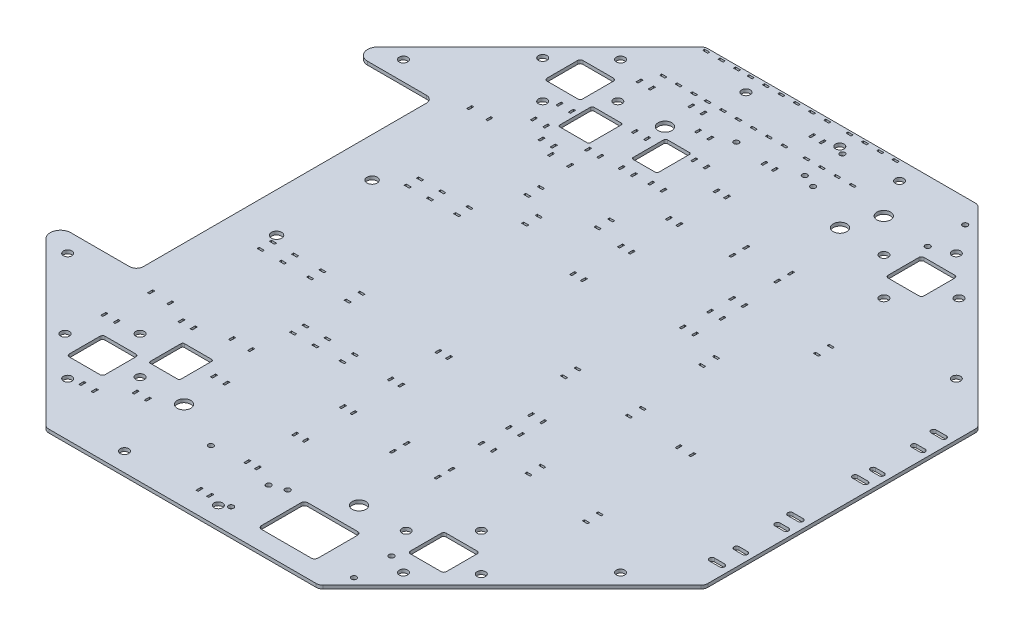
SolidWorks part; units mm, degrees
ref_plane "前视基准面" through (0, 0, 0) normal (0, 0, 1) x (1, 0, 0)
ref_plane "上视基准面" through (0, 0, 0) normal (0, 1, 0) x (1, 0, 0)
ref_plane "右视基准面" through (0, 0, 0) normal (1, 0, 0) x (0, 0, -1)
other "Configuration Table"
ref_plane "基准面1" through (0, 0, 0) normal (0, -1, 0) x (1, 0, 0)
sketch "草图1" plane through (0, 0, 0) normal (0, -1, 0) x (1, 0, 0)
  line L0 (-175.8944, -97.2426) -> (-81.1716, -191.9655)
  line L1 (-78.3431, -193.1371) -> (78.3431, -193.1371)
  line L2 (81.1716, -191.9655) -> (191.9655, -81.1716)
  line L3 (193.1371, -78.3431) -> (193.1371, 78.3431)
  line L4 (191.9655, 81.1716) -> (81.1716, 191.9655)
  line L5 (78.3431, 193.1371) -> (-78.3431, 193.1371)
  line L6 (-81.1716, 191.9655) -> (-175.8944, 97.2426)
  line L7 (-171.6518, 87) -> (-137.1371, 87)
  line L8 (-133.1371, 83) -> (-133.1371, -83)
  line L9 (-137.1371, -87) -> (-171.6518, -87)
  line L10 (182.1371, -63.5) -> (188.1371, -63.5)
  line L11 (188.1371, -66.5) -> (182.1371, -66.5)
  line L12 (182.1371, -17.5) -> (188.1371, -17.5)
  line L13 (188.1371, -20.5) -> (182.1371, -20.5)
  line L14 (182.1371, 66.5) -> (188.1371, 66.5)
  line L15 (188.1371, 63.5) -> (182.1371, 63.5)
  line L16 (182.1371, 20.5) -> (188.1371, 20.5)
  line L17 (188.1371, 17.5) -> (182.1371, 17.5)
  line L18 (183.6371, 53.5) -> (188.6371, 53.5)
  line L19 (188.6371, 50.5) -> (183.6371, 50.5)
  line L20 (188.6371, 26.5) -> (183.6371, 26.5)
  line L21 (183.6371, 29.5) -> (188.6371, 29.5)
  line L22 (188.6371, -53.5) -> (183.6371, -53.5)
  line L23 (183.6371, -50.5) -> (188.6371, -50.5)
  line L24 (183.6371, -26.5) -> (188.6371, -26.5)
  line L25 (188.6371, -29.5) -> (183.6371, -29.5)
  line L26 (-45, -134) -> (-45, -116)
  line L27 (-44, -115) -> (-31, -115)
  line L28 (-30, -116) -> (-30, -134)
  line L29 (-31, -135) -> (-44, -135)
  line L30 (-95, -43.2) -> (-98, -43.2)
  line L31 (-98, -43.2) -> (-98, -42)
  line L32 (-98, -42) -> (-95, -42)
  line L33 (-95, -42) -> (-95, -43.2)
  line L34 (-95, -36) -> (-98, -36)
  line L35 (-98, -36) -> (-98, -34.8)
  line L36 (-98, -34.8) -> (-95, -34.8)
  line L37 (-95, -34.8) -> (-95, -36)
  line L38 (-82, -43.2) -> (-85, -43.2)
  line L39 (-85, -43.2) -> (-85, -42)
  line L40 (-85, -42) -> (-82, -42)
  line L41 (-82, -42) -> (-82, -43.2)
  line L42 (-82, -36) -> (-85, -36)
  line L43 (-85, -36) -> (-85, -34.8)
  line L44 (-85, -34.8) -> (-82, -34.8)
  line L45 (-82, -34.8) -> (-82, -36)
  line L46 (-66, -43.2) -> (-69, -43.2)
  line L47 (-69, -43.2) -> (-69, -42)
  line L48 (-69, -42) -> (-66, -42)
  line L49 (-66, -42) -> (-66, -43.2)
  line L50 (-66, -36) -> (-69, -36)
  line L51 (-69, -36) -> (-69, -34.8)
  line L52 (-69, -34.8) -> (-66, -34.8)
  line L53 (-66, -34.8) -> (-66, -36)
  line L54 (-54, 65) -> (-57, 65)
  line L55 (-57, 65) -> (-57, 66.2)
  line L56 (-57, 66.2) -> (-54, 66.2)
  line L57 (-54, 66.2) -> (-54, 65)
  line L58 (-54, 72.2) -> (-57, 72.2)
  line L59 (-57, 72.2) -> (-57, 73.4)
  line L60 (-57, 73.4) -> (-54, 73.4)
  line L61 (-54, 73.4) -> (-54, 72.2)
  line L62 (-41, 65) -> (-44, 65)
  line L63 (-44, 65) -> (-44, 66.2)
  line L64 (-44, 66.2) -> (-41, 66.2)
  line L65 (-41, 66.2) -> (-41, 65)
  line L66 (-41, 72.2) -> (-44, 72.2)
  line L67 (-44, 72.2) -> (-44, 73.4)
  line L68 (-44, 73.4) -> (-41, 73.4)
  line L69 (-41, 73.4) -> (-41, 72.2)
  line L70 (-25, 65) -> (-28, 65)
  line L71 (-28, 65) -> (-28, 66.2)
  line L72 (-28, 66.2) -> (-25, 66.2)
  line L73 (-25, 66.2) -> (-25, 65)
  line L74 (-25, 72.2) -> (-28, 72.2)
  line L75 (-28, 72.2) -> (-28, 73.4)
  line L76 (-28, 73.4) -> (-25, 73.4)
  line L77 (-25, 73.4) -> (-25, 72.2)
  line L78 (-106, 32) -> (-109, 32)
  line L79 (-109, 32) -> (-109, 33.2)
  line L80 (-109, 33.2) -> (-106, 33.2)
  line L81 (-106, 33.2) -> (-106, 32)
  line L82 (-106, 39.2) -> (-109, 39.2)
  line L83 (-109, 39.2) -> (-109, 40.4)
  line L84 (-109, 40.4) -> (-106, 40.4)
  line L85 (-106, 40.4) -> (-106, 39.2)
  line L86 (-93, 32) -> (-96, 32)
  line L87 (-96, 32) -> (-96, 33.2)
  line L88 (-96, 33.2) -> (-93, 33.2)
  line L89 (-93, 33.2) -> (-93, 32)
  line L90 (-93, 39.2) -> (-96, 39.2)
  line L91 (-96, 39.2) -> (-96, 40.4)
  line L92 (-96, 40.4) -> (-93, 40.4)
  line L93 (-93, 40.4) -> (-93, 39.2)
  line L94 (-77, 32) -> (-80, 32)
  line L95 (-80, 32) -> (-80, 33.2)
  line L96 (-80, 33.2) -> (-77, 33.2)
  line L97 (-77, 33.2) -> (-77, 32)
  line L98 (-77, 39.2) -> (-80, 39.2)
  line L99 (-80, 39.2) -> (-80, 40.4)
  line L100 (-80, 40.4) -> (-77, 40.4)
  line L101 (-77, 40.4) -> (-77, 39.2)
  line L102 (63.4, -72) -> (63.4, -75)
  line L103 (63.4, -75) -> (62.2, -75)
  line L104 (62.2, -75) -> (62.2, -72)
  line L105 (62.2, -72) -> (63.4, -72)
  line L106 (56.2, -72) -> (56.2, -75)
  line L107 (56.2, -75) -> (55, -75)
  line L108 (55, -75) -> (55, -72)
  line L109 (55, -72) -> (56.2, -72)
  line L110 (63.4, -59) -> (63.4, -62)
  line L111 (63.4, -62) -> (62.2, -62)
  line L112 (62.2, -62) -> (62.2, -59)
  line L113 (62.2, -59) -> (63.4, -59)
  line L114 (56.2, -59) -> (56.2, -62)
  line L115 (56.2, -62) -> (55, -62)
  line L116 (55, -62) -> (55, -59)
  line L117 (55, -59) -> (56.2, -59)
  line L118 (63.4, -43) -> (63.4, -46)
  line L119 (63.4, -46) -> (62.2, -46)
  line L120 (62.2, -46) -> (62.2, -43)
  line L121 (62.2, -43) -> (63.4, -43)
  line L122 (56.2, -43) -> (56.2, -46)
  line L123 (56.2, -46) -> (55, -46)
  line L124 (55, -46) -> (55, -43)
  line L125 (55, -43) -> (56.2, -43)
  line L126 (63.4, 46) -> (63.4, 43)
  line L127 (63.4, 43) -> (62.2, 43)
  line L128 (62.2, 43) -> (62.2, 46)
  line L129 (62.2, 46) -> (63.4, 46)
  line L130 (56.2, 46) -> (56.2, 43)
  line L131 (56.2, 43) -> (55, 43)
  line L132 (55, 43) -> (55, 46)
  line L133 (55, 46) -> (56.2, 46)
  line L134 (63.4, 59) -> (63.4, 56)
  line L135 (63.4, 56) -> (62.2, 56)
  line L136 (62.2, 56) -> (62.2, 59)
  line L137 (62.2, 59) -> (63.4, 59)
  line L138 (56.2, 59) -> (56.2, 56)
  line L139 (56.2, 56) -> (55, 56)
  line L140 (55, 56) -> (55, 59)
  line L141 (55, 59) -> (56.2, 59)
  line L142 (63.4, 75) -> (63.4, 72)
  line L143 (63.4, 72) -> (62.2, 72)
  line L144 (62.2, 72) -> (62.2, 75)
  line L145 (62.2, 75) -> (63.4, 75)
  line L146 (56.2, 75) -> (56.2, 72)
  line L147 (56.2, 72) -> (55, 72)
  line L148 (55, 72) -> (55, 75)
  line L149 (55, 75) -> (56.2, 75)
  line L150 (-70, 92) -> (-71.2, 92)
  line L151 (-71.2, 92) -> (-71.2, 95)
  line L152 (-71.2, 95) -> (-70, 95)
  line L153 (-70, 95) -> (-70, 92)
  line L154 (-58.8, 92) -> (-60, 92)
  line L155 (-60, 92) -> (-60, 95)
  line L156 (-60, 95) -> (-58.8, 95)
  line L157 (-58.8, 95) -> (-58.8, 92)
  line L158 (-106.2, 92) -> (-107.4, 92)
  line L159 (-107.4, 92) -> (-107.4, 95)
  line L160 (-107.4, 95) -> (-106.2, 95)
  line L161 (-106.2, 95) -> (-106.2, 92)
  line L162 (-117.4, 92) -> (-118.6, 92)
  line L163 (-118.6, 92) -> (-118.6, 95)
  line L164 (-118.6, 95) -> (-117.4, 95)
  line L165 (-117.4, 95) -> (-117.4, 92)
  line L166 (-70, -92) -> (-70, -95)
  line L167 (-70, -95) -> (-71.2, -95)
  line L168 (-71.2, -95) -> (-71.2, -92)
  line L169 (-71.2, -92) -> (-70, -92)
  line L170 (-58.8, -95) -> (-60, -95)
  line L171 (-60, -95) -> (-60, -92)
  line L172 (-60, -92) -> (-58.8, -92)
  line L173 (-58.8, -92) -> (-58.8, -95)
  line L174 (-106.2, -92) -> (-106.2, -95)
  line L175 (-106.2, -95) -> (-107.4, -95)
  line L176 (-107.4, -95) -> (-107.4, -92)
  line L177 (-107.4, -92) -> (-106.2, -92)
  line L178 (-117.4, -92) -> (-117.4, -95)
  line L179 (-117.4, -95) -> (-118.6, -95)
  line L180 (-118.6, -95) -> (-118.6, -92)
  line L181 (-118.6, -92) -> (-117.4, -92)
  line L182 (-3, 150) -> (-4.2, 150)
  line L183 (-4.2, 150) -> (-4.2, 153)
  line L184 (-4.2, 153) -> (-3, 153)
  line L185 (-3, 153) -> (-3, 150)
  line L186 (3.2, 150) -> (2, 150)
  line L187 (2, 150) -> (2, 153)
  line L188 (2, 153) -> (3.2, 153)
  line L189 (3.2, 153) -> (3.2, 150)
  line L190 (-4.2, 122) -> (-4.2, 125)
  line L191 (-4.2, 125) -> (-3, 125)
  line L192 (-3, 125) -> (-3, 122)
  line L193 (-3, 122) -> (-4.2, 122)
  line L194 (3.2, 122) -> (2, 122)
  line L195 (2, 122) -> (2, 125)
  line L196 (2, 125) -> (3.2, 125)
  line L197 (3.2, 125) -> (3.2, 122)
  line L198 (-3, 94) -> (-4.2, 94)
  line L199 (-4.2, 94) -> (-4.2, 97)
  line L200 (-4.2, 97) -> (-3, 97)
  line L201 (-3, 97) -> (-3, 94)
  line L202 (3.2, 94) -> (2, 94)
  line L203 (2, 94) -> (2, 97)
  line L204 (2, 97) -> (3.2, 97)
  line L205 (3.2, 97) -> (3.2, 94)
  line L206 (-4.2, 178) -> (-4.2, 181)
  line L207 (-4.2, 181) -> (-3, 181)
  line L208 (-3, 181) -> (-3, 178)
  line L209 (-3, 178) -> (-4.2, 178)
  line L210 (2, 178) -> (2, 181)
  line L211 (2, 181) -> (3.2, 181)
  line L212 (3.2, 181) -> (3.2, 178)
  line L213 (3.2, 178) -> (2, 178)
  line L214 (-4.2, 66) -> (-4.2, 69)
  line L215 (-4.2, 69) -> (-3, 69)
  line L216 (-3, 69) -> (-3, 66)
  line L217 (-3, 66) -> (-4.2, 66)
  line L218 (2, 66) -> (2, 69)
  line L219 (2, 69) -> (3.2, 69)
  line L220 (3.2, 69) -> (3.2, 66)
  line L221 (3.2, 66) -> (2, 66)
  line L222 (-4.2, 38) -> (-4.2, 41)
  line L223 (-4.2, 41) -> (-3, 41)
  line L224 (-3, 41) -> (-3, 38)
  line L225 (-3, 38) -> (-4.2, 38)
  line L226 (2, 38) -> (2, 41)
  line L227 (2, 41) -> (3.2, 41)
  line L228 (3.2, 41) -> (3.2, 38)
  line L229 (3.2, 38) -> (2, 38)
  line L230 (-3, -150) -> (-3, -153)
  line L231 (-3, -153) -> (-4.2, -153)
  line L232 (-4.2, -153) -> (-4.2, -150)
  line L233 (-4.2, -150) -> (-3, -150)
  line L234 (3.2, -150) -> (3.2, -153)
  line L235 (3.2, -153) -> (2, -153)
  line L236 (2, -153) -> (2, -150)
  line L237 (2, -150) -> (3.2, -150)
  line L238 (-4.2, -122) -> (-3, -122)
  line L239 (-3, -122) -> (-3, -125)
  line L240 (-3, -125) -> (-4.2, -125)
  line L241 (-4.2, -125) -> (-4.2, -122)
  line L242 (3.2, -122) -> (3.2, -125)
  line L243 (3.2, -125) -> (2, -125)
  line L244 (2, -125) -> (2, -122)
  line L245 (2, -122) -> (3.2, -122)
  line L246 (-3, -94) -> (-3, -97)
  line L247 (-3, -97) -> (-4.2, -97)
  line L248 (-4.2, -97) -> (-4.2, -94)
  line L249 (-4.2, -94) -> (-3, -94)
  line L250 (3.2, -94) -> (3.2, -97)
  line L251 (3.2, -97) -> (2, -97)
  line L252 (2, -97) -> (2, -94)
  line L253 (2, -94) -> (3.2, -94)
  line L254 (-4.2, -178) -> (-3, -178)
  line L255 (-3, -178) -> (-3, -181)
  line L256 (-3, -181) -> (-4.2, -181)
  line L257 (-4.2, -181) -> (-4.2, -178)
  line L258 (2, -178) -> (3.2, -178)
  line L259 (3.2, -178) -> (3.2, -181)
  line L260 (3.2, -181) -> (2, -181)
  line L261 (2, -181) -> (2, -178)
  line L262 (-4.2, -66) -> (-3, -66)
  line L263 (-3, -66) -> (-3, -69)
  line L264 (-3, -69) -> (-4.2, -69)
  line L265 (-4.2, -69) -> (-4.2, -66)
  line L266 (2, -66) -> (3.2, -66)
  line L267 (3.2, -66) -> (3.2, -69)
  line L268 (3.2, -69) -> (2, -69)
  line L269 (2, -69) -> (2, -66)
  line L270 (-4.2, -38) -> (-3, -38)
  line L271 (-3, -38) -> (-3, -41)
  line L272 (-3, -41) -> (-4.2, -41)
  line L273 (-4.2, -41) -> (-4.2, -38)
  line L274 (2, -38) -> (3.2, -38)
  line L275 (3.2, -38) -> (3.2, -41)
  line L276 (3.2, -41) -> (2, -41)
  line L277 (2, -41) -> (2, -38)
  line L278 (60.6, -102) -> (60.6, -105)
  line L279 (60.6, -105) -> (59.4, -105)
  line L280 (59.4, -105) -> (59.4, -102)
  line L281 (59.4, -102) -> (60.6, -102)
  line L282 (34.4, -102) -> (34.4, -105)
  line L283 (34.4, -105) -> (33.2, -105)
  line L284 (33.2, -105) -> (33.2, -102)
  line L285 (33.2, -102) -> (34.4, -102)
  line L286 (60.6, -94) -> (60.6, -97)
  line L287 (60.6, -97) -> (59.4, -97)
  line L288 (59.4, -97) -> (59.4, -94)
  line L289 (59.4, -94) -> (60.6, -94)
  line L290 (34.4, -94) -> (34.4, -97)
  line L291 (34.4, -97) -> (33.2, -97)
  line L292 (33.2, -97) -> (33.2, -94)
  line L293 (33.2, -94) -> (34.4, -94)
  line L294 (60.6, 102) -> (59.4, 102)
  line L295 (59.4, 102) -> (59.4, 105)
  line L296 (59.4, 105) -> (60.6, 105)
  line L297 (60.6, 105) -> (60.6, 102)
  line L298 (34.4, 102) -> (33.2, 102)
  line L299 (33.2, 102) -> (33.2, 105)
  line L300 (33.2, 105) -> (34.4, 105)
  line L301 (34.4, 105) -> (34.4, 102)
  line L302 (60.6, 94) -> (59.4, 94)
  line L303 (59.4, 94) -> (59.4, 97)
  line L304 (59.4, 97) -> (60.6, 97)
  line L305 (60.6, 97) -> (60.6, 94)
  line L306 (34.4, 94) -> (33.2, 94)
  line L307 (33.2, 94) -> (33.2, 97)
  line L308 (33.2, 97) -> (34.4, 97)
  line L309 (34.4, 97) -> (34.4, 94)
  line L310 (-44.3, -57.9) -> (-41.3, -57.9)
  line L311 (-41.3, -57.9) -> (-41.3, -59.1)
  line L312 (-41.3, -59.1) -> (-44.3, -59.1)
  line L313 (-44.3, -59.1) -> (-44.3, -57.9)
  line L314 (-44.3, -49.9) -> (-41.3, -49.9)
  line L315 (-41.3, -49.9) -> (-41.3, -51.1)
  line L316 (-41.3, -51.1) -> (-44.3, -51.1)
  line L317 (-44.3, -51.1) -> (-44.3, -49.9)
  line L318 (-58.3, -73.1) -> (-55.3, -73.1)
  line L319 (-55.3, -73.1) -> (-55.3, -74.3)
  line L320 (-55.3, -74.3) -> (-58.3, -74.3)
  line L321 (-58.3, -74.3) -> (-58.3, -73.1)
  line L322 (-58.3, -65.1) -> (-55.3, -65.1)
  line L323 (-55.3, -65.1) -> (-55.3, -66.3)
  line L324 (-55.3, -66.3) -> (-58.3, -66.3)
  line L325 (-58.3, -66.3) -> (-58.3, -65.1)
  line L326 (-21.2, -77.2386) -> (-18.2, -77.2386)
  line L327 (-18.2, -77.2386) -> (-18.2, -78.4386)
  line L328 (-18.2, -78.4386) -> (-21.2, -78.4386)
  line L329 (-21.2, -78.4386) -> (-21.2, -77.2386)
  line L330 (-21.2, -69.2386) -> (-18.2, -69.2386)
  line L331 (-18.2, -69.2386) -> (-18.2, -70.4386)
  line L332 (-18.2, -70.4386) -> (-21.2, -70.4386)
  line L333 (-21.2, -70.4386) -> (-21.2, -69.2386)
  line L334 (-57.2, 33.2) -> (-54.2, 33.2)
  line L335 (-54.2, 33.2) -> (-54.2, 32)
  line L336 (-54.2, 32) -> (-57.2, 32)
  line L337 (-57.2, 32) -> (-57.2, 33.2)
  line L338 (-57.2, 41.2) -> (-54.2, 41.2)
  line L339 (-54.2, 41.2) -> (-54.2, 40)
  line L340 (-54.2, 40) -> (-57.2, 40)
  line L341 (-57.2, 40) -> (-57.2, 41.2)
  line L342 (83.6, 68) -> (86.6, 68)
  line L343 (86.6, 68) -> (86.6, 66.8)
  line L344 (86.6, 66.8) -> (83.6, 66.8)
  line L345 (83.6, 66.8) -> (83.6, 68)
  line L346 (83.6, 76) -> (86.6, 76)
  line L347 (86.6, 76) -> (86.6, 74.8)
  line L348 (86.6, 74.8) -> (83.6, 74.8)
  line L349 (83.6, 74.8) -> (83.6, 76)
  line L350 (124.6, 75.3293) -> (127.6, 75.3293)
  line L351 (127.6, 75.3293) -> (127.6, 74.1293)
  line L352 (127.6, 74.1293) -> (124.6, 74.1293)
  line L353 (124.6, 74.1293) -> (124.6, 75.3293)
  line L354 (124.6, 83.3293) -> (127.6, 83.3293)
  line L355 (127.6, 83.3293) -> (127.6, 82.1293)
  line L356 (127.6, 82.1293) -> (124.6, 82.1293)
  line L357 (124.6, 82.1293) -> (124.6, 83.3293)
  line L358 (83.6, 9.2) -> (86.6, 9.2)
  line L359 (86.6, 9.2) -> (86.6, 8)
  line L360 (86.6, 8) -> (83.6, 8)
  line L361 (83.6, 8) -> (83.6, 9.2)
  line L362 (83.6, 17.2) -> (86.6, 17.2)
  line L363 (86.6, 17.2) -> (86.6, 16)
  line L364 (86.6, 16) -> (83.6, 16)
  line L365 (83.6, 16) -> (83.6, 17.2)
  line L366 (44.6, 8.2) -> (47.6, 8.2)
  line L367 (47.6, 8.2) -> (47.6, 7)
  line L368 (47.6, 7) -> (44.6, 7)
  line L369 (44.6, 7) -> (44.6, 8.2)
  line L370 (44.6, 16.2) -> (47.6, 16.2)
  line L371 (47.6, 16.2) -> (47.6, 15)
  line L372 (47.6, 15) -> (44.6, 15)
  line L373 (44.6, 15) -> (44.6, 16.2)
  line L374 (122.6, 16) -> (122.6, 19)
  line L375 (122.6, 19) -> (123.8, 19)
  line L376 (123.8, 19) -> (123.8, 16)
  line L377 (123.8, 16) -> (122.6, 16)
  line L378 (114.6, 16) -> (114.6, 19)
  line L379 (114.6, 19) -> (115.8, 19)
  line L380 (115.8, 19) -> (115.8, 16)
  line L381 (115.8, 16) -> (114.6, 16)
  line L382 (79.2663, -38.2) -> (82.2663, -38.2)
  line L383 (82.2663, -38.2) -> (82.2663, -39.4)
  line L384 (82.2663, -39.4) -> (79.2663, -39.4)
  line L385 (79.2663, -39.4) -> (79.2663, -38.2)
  line L386 (79.2663, -30) -> (82.2663, -30)
  line L387 (82.2663, -30) -> (82.2663, -31.2)
  line L388 (82.2663, -31.2) -> (79.2663, -31.2)
  line L389 (79.2663, -31.2) -> (79.2663, -30)
  line L390 (107.2663, -77.4) -> (110.2663, -77.4)
  line L391 (110.2663, -77.4) -> (110.2663, -78.6)
  line L392 (110.2663, -78.6) -> (107.2663, -78.6)
  line L393 (107.2663, -78.6) -> (107.2663, -77.4)
  line L394 (107.2663, -69.4) -> (110.2663, -69.4)
  line L395 (110.2663, -69.4) -> (110.2663, -70.6)
  line L396 (110.2663, -70.6) -> (107.2663, -70.6)
  line L397 (107.2663, -70.6) -> (107.2663, -69.4)
  line L398 (-110.5, 131) -> (-110.5, 149)
  line L399 (-109, 150.5) -> (-91, 150.5)
  line L400 (-89.5, 149) -> (-89.5, 131)
  line L401 (-91, 129.5) -> (-109, 129.5)
  line L402 (-110.5, -149) -> (-110.5, -131)
  line L403 (-109, -129.5) -> (-91, -129.5)
  line L404 (-89.5, -131) -> (-89.5, -149)
  line L405 (-91, -150.5) -> (-109, -150.5)
  line L406 (109, -150.5) -> (91, -150.5)
  line L407 (89.5, -149) -> (89.5, -131)
  line L408 (91, -129.5) -> (109, -129.5)
  line L409 (110.5, -131) -> (110.5, -149)
  line L410 (109, 129.5) -> (91, 129.5)
  line L411 (89.5, 131) -> (89.5, 149)
  line L412 (91, 150.5) -> (109, 150.5)
  line L413 (110.5, 149) -> (110.5, 131)
  line L414 (-83, -129) -> (-83, -111)
  line L415 (-82, -110) -> (-66, -110)
  line L416 (-65, -111) -> (-65, -129)
  line L417 (-66, -130) -> (-82, -130)
  line L418 (-83, 111) -> (-83, 129)
  line L419 (-82, 130) -> (-66, 130)
  line L420 (-65, 129) -> (-65, 111)
  line L421 (-66, 110) -> (-82, 110)
  line L426 (-94.2, -123) -> (-94.2, -120)
  line L427 (-94.2, -120) -> (-93, -120)
  line L428 (-93, -120) -> (-93, -123)
  line L429 (-93, -123) -> (-94.2, -123)
  line L430 (-87, -123) -> (-87, -120)
  line L431 (-87, -120) -> (-85.8, -120)
  line L432 (-85.8, -120) -> (-85.8, -123)
  line L433 (-85.8, -123) -> (-87, -123)
  line L434 (-94.2, -108) -> (-94.2, -105)
  line L435 (-94.2, -105) -> (-93, -105)
  line L436 (-93, -105) -> (-93, -108)
  line L437 (-93, -108) -> (-94.2, -108)
  line L438 (-87, -108) -> (-87, -105)
  line L439 (-87, -105) -> (-85.8, -105)
  line L440 (-85.8, -105) -> (-85.8, -108)
  line L441 (-85.8, -108) -> (-87, -108)
  line L442 (-81.8, -100) -> (-81.8, -97)
  line L443 (-81.8, -97) -> (-80.6, -97)
  line L444 (-80.6, -97) -> (-80.6, -100)
  line L445 (-80.6, -100) -> (-81.8, -100)
  line L446 (-74.6, -100) -> (-74.6, -97)
  line L447 (-74.6, -97) -> (-73.4, -97)
  line L448 (-73.4, -97) -> (-73.4, -100)
  line L449 (-73.4, -100) -> (-74.6, -100)
  line L450 (-62.9553, -108.4646) -> (-62.9553, -105.4646)
  line L451 (-62.9553, -105.4646) -> (-61.7553, -105.4646)
  line L452 (-61.7553, -105.4646) -> (-61.7553, -108.4646)
  line L453 (-61.7553, -108.4646) -> (-62.9553, -108.4646)
  line L454 (-55.7553, -108.4646) -> (-55.7553, -105.4646)
  line L455 (-55.7553, -105.4646) -> (-54.5553, -105.4646)
  line L456 (-54.5553, -105.4646) -> (-54.5553, -108.4646)
  line L457 (-54.5553, -108.4646) -> (-55.7553, -108.4646)
  line L458 (-43.8435, -108.9355) -> (-43.8435, -105.9355)
  line L459 (-43.8435, -105.9355) -> (-42.6435, -105.9355)
  line L460 (-42.6435, -105.9355) -> (-42.6435, -108.9355)
  line L461 (-42.6435, -108.9355) -> (-43.8435, -108.9355)
  line L462 (-36.6435, -108.9355) -> (-36.6435, -105.9355)
  line L463 (-36.6435, -105.9355) -> (-35.4435, -105.9355)
  line L464 (-35.4435, -105.9355) -> (-35.4435, -108.9355)
  line L465 (-35.4435, -108.9355) -> (-36.6435, -108.9355)
  line L466 (-58.2819, -131.1727) -> (-58.2819, -128.1727)
  line L467 (-58.2819, -128.1727) -> (-57.0819, -128.1727)
  line L468 (-57.0819, -128.1727) -> (-57.0819, -131.1727)
  line L469 (-57.0819, -131.1727) -> (-58.2819, -131.1727)
  line L470 (-51.0819, -131.1727) -> (-51.0819, -128.1727)
  line L471 (-51.0819, -128.1727) -> (-49.8819, -128.1727)
  line L472 (-49.8819, -128.1727) -> (-49.8819, -131.1727)
  line L473 (-49.8819, -131.1727) -> (-51.0819, -131.1727)
  line L474 (-27.2743, -109.7819) -> (-27.2743, -106.7819)
  line L475 (-27.2743, -106.7819) -> (-26.0743, -106.7819)
  line L476 (-26.0743, -106.7819) -> (-26.0743, -109.7819)
  line L477 (-26.0743, -109.7819) -> (-27.2743, -109.7819)
  line L478 (-20.0743, -109.7819) -> (-20.0743, -106.7819)
  line L479 (-20.0743, -106.7819) -> (-18.8743, -106.7819)
  line L480 (-18.8743, -106.7819) -> (-18.8743, -109.7819)
  line L481 (-18.8743, -109.7819) -> (-20.0743, -109.7819)
  line L482 (-26.4312, -134.2323) -> (-26.4312, -131.2323)
  line L483 (-26.4312, -131.2323) -> (-25.2312, -131.2323)
  line L484 (-25.2312, -131.2323) -> (-25.2312, -134.2323)
  line L485 (-25.2312, -134.2323) -> (-26.4312, -134.2323)
  line L486 (-19.2312, -134.2323) -> (-19.2312, -131.2323)
  line L487 (-19.2312, -131.2323) -> (-18.0312, -131.2323)
  line L488 (-18.0312, -131.2323) -> (-18.0312, -134.2323)
  line L489 (-18.0312, -134.2323) -> (-19.2312, -134.2323)
  line L490 (-82.5198, -158.1886) -> (-82.5198, -155.1886)
  line L491 (-82.5198, -155.1886) -> (-81.3198, -155.1886)
  line L492 (-81.3198, -155.1886) -> (-81.3198, -158.1886)
  line L493 (-81.3198, -158.1886) -> (-82.5198, -158.1886)
  line L494 (-75.3198, -158.1886) -> (-75.3198, -155.1886)
  line L495 (-75.3198, -155.1886) -> (-74.1198, -155.1886)
  line L496 (-74.1198, -155.1886) -> (-74.1198, -158.1886)
  line L497 (-74.1198, -158.1886) -> (-75.3198, -158.1886)
  line L498 (-54.7234, -160.6916) -> (-54.7234, -157.6916)
  line L499 (-54.7234, -157.6916) -> (-53.5234, -157.6916)
  line L500 (-53.5234, -157.6916) -> (-53.5234, -160.6916)
  line L501 (-53.5234, -160.6916) -> (-54.7234, -160.6916)
  line L502 (-47.5234, -160.6916) -> (-47.5234, -157.6916)
  line L503 (-47.5234, -157.6916) -> (-46.3234, -157.6916)
  line L504 (-46.3234, -157.6916) -> (-46.3234, -160.6916)
  line L505 (-46.3234, -160.6916) -> (-47.5234, -160.6916)
  line L506 (-39.9688, -149.8892) -> (-39.9688, -146.8892)
  line L507 (-39.9688, -146.8892) -> (-38.7688, -146.8892)
  line L508 (-38.7688, -146.8892) -> (-38.7688, -149.8892)
  line L509 (-38.7688, -149.8892) -> (-39.9688, -149.8892)
  line L510 (-32.7688, -149.8892) -> (-32.7688, -146.8892)
  line L511 (-32.7688, -146.8892) -> (-31.5688, -146.8892)
  line L512 (-31.5688, -146.8892) -> (-31.5688, -149.8892)
  line L513 (-31.5688, -149.8892) -> (-32.7688, -149.8892)
  line L514 (-95.0603, 97.7824) -> (-95.0603, 100.7824)
  line L515 (-95.0603, 100.7824) -> (-93.8603, 100.7824)
  line L516 (-93.8603, 100.7824) -> (-93.8603, 97.7824)
  line L517 (-93.8603, 97.7824) -> (-95.0603, 97.7824)
  line L518 (-87.8603, 97.7824) -> (-87.8603, 100.7824)
  line L519 (-87.8603, 100.7824) -> (-86.6603, 100.7824)
  line L520 (-86.6603, 100.7824) -> (-86.6603, 97.7824)
  line L521 (-86.6603, 97.7824) -> (-87.8603, 97.7824)
  line L522 (-120.8807, 117.1148) -> (-120.8807, 120.1148)
  line L523 (-120.8807, 120.1148) -> (-119.6807, 120.1148)
  line L524 (-119.6807, 120.1148) -> (-119.6807, 117.1148)
  line L525 (-119.6807, 117.1148) -> (-120.8807, 117.1148)
  line L526 (-113.6807, 117.1148) -> (-113.6807, 120.1148)
  line L527 (-113.6807, 120.1148) -> (-112.4807, 120.1148)
  line L528 (-112.4807, 120.1148) -> (-112.4807, 117.1148)
  line L529 (-112.4807, 117.1148) -> (-113.6807, 117.1148)
  line L530 (-57.4823, 116.2914) -> (-57.4823, 119.2914)
  line L531 (-57.4823, 119.2914) -> (-56.2823, 119.2914)
  line L532 (-56.2823, 119.2914) -> (-56.2823, 116.2914)
  line L533 (-56.2823, 116.2914) -> (-57.4823, 116.2914)
  line L534 (-50.2823, 116.2914) -> (-50.2823, 119.2914)
  line L535 (-50.2823, 119.2914) -> (-49.0823, 119.2914)
  line L536 (-49.0823, 119.2914) -> (-49.0823, 116.2914)
  line L537 (-49.0823, 116.2914) -> (-50.2823, 116.2914)
  line L538 (-72.3027, 147.4142) -> (-72.3027, 150.4142)
  line L539 (-72.3027, 150.4142) -> (-71.1027, 150.4142)
  line L540 (-71.1027, 150.4142) -> (-71.1027, 147.4142)
  line L541 (-71.1027, 147.4142) -> (-72.3027, 147.4142)
  line L542 (-65.1027, 147.4142) -> (-65.1027, 150.4142)
  line L543 (-65.1027, 150.4142) -> (-63.9027, 150.4142)
  line L544 (-63.9027, 150.4142) -> (-63.9027, 147.4142)
  line L545 (-63.9027, 147.4142) -> (-65.1027, 147.4142)
  line L546 (-92.2279, 158.6119) -> (-92.2279, 161.6119)
  line L547 (-92.2279, 161.6119) -> (-91.0279, 161.6119)
  line L548 (-91.0279, 161.6119) -> (-91.0279, 158.6119)
  line L549 (-91.0279, 158.6119) -> (-92.2279, 158.6119)
  line L550 (-85.0279, 158.6119) -> (-85.0279, 161.6119)
  line L551 (-85.0279, 161.6119) -> (-83.8279, 161.6119)
  line L552 (-83.8279, 161.6119) -> (-83.8279, 158.6119)
  line L553 (-83.8279, 158.6119) -> (-85.0279, 158.6119)
  line L554 (-58, -165.5371) -> (-58, -166.7371)
  line L555 (-58, -166.7371) -> (-61, -166.7371)
  line L556 (-61, -166.7371) -> (-61, -165.5371)
  line L557 (-61, -165.5371) -> (-58, -165.5371)
  line L558 (-50, -165.5371) -> (-50, -166.7371)
  line L559 (-50, -166.7371) -> (-53, -166.7371)
  line L560 (-53, -166.7371) -> (-53, -165.5371)
  line L561 (-53, -165.5371) -> (-50, -165.5371)
  line L562 (-41, -165.5371) -> (-41, -166.7371)
  line L563 (-41, -166.7371) -> (-44, -166.7371)
  line L564 (-44, -166.7371) -> (-44, -165.5371)
  line L565 (-44, -165.5371) -> (-41, -165.5371)
  line L566 (-32, -165.5371) -> (-32, -166.7371)
  line L567 (-32, -166.7371) -> (-35, -166.7371)
  line L568 (-35, -166.7371) -> (-35, -165.5371)
  line L569 (-35, -165.5371) -> (-32, -165.5371)
  line L570 (-23, -165.5371) -> (-23, -166.7371)
  line L571 (-23, -166.7371) -> (-26, -166.7371)
  line L572 (-26, -166.7371) -> (-26, -165.5371)
  line L573 (-26, -165.5371) -> (-23, -165.5371)
  line L574 (-14, -165.5371) -> (-14, -166.7371)
  line L575 (-14, -166.7371) -> (-17, -166.7371)
  line L576 (-17, -166.7371) -> (-17, -165.5371)
  line L577 (-17, -165.5371) -> (-14, -165.5371)
  line L578 (-5, -165.5371) -> (-5, -166.7371)
  line L579 (-5, -166.7371) -> (-8, -166.7371)
  line L580 (-8, -166.7371) -> (-8, -165.5371)
  line L581 (-8, -165.5371) -> (-5, -165.5371)
  line L582 (35, -166.7371) -> (32, -166.7371)
  line L583 (32, -166.7371) -> (32, -165.5371)
  line L584 (32, -165.5371) -> (35, -165.5371)
  line L585 (35, -165.5371) -> (35, -166.7371)
  line L586 (26, -166.7371) -> (23, -166.7371)
  line L587 (23, -166.7371) -> (23, -165.5371)
  line L588 (23, -165.5371) -> (26, -165.5371)
  line L589 (26, -165.5371) -> (26, -166.7371)
  line L590 (17, -166.7371) -> (14, -166.7371)
  line L591 (14, -166.7371) -> (14, -165.5371)
  line L592 (14, -165.5371) -> (17, -165.5371)
  line L593 (17, -165.5371) -> (17, -166.7371)
  line L594 (8, -166.7371) -> (5, -166.7371)
  line L595 (5, -166.7371) -> (5, -165.5371)
  line L596 (5, -165.5371) -> (8, -165.5371)
  line L597 (8, -165.5371) -> (8, -166.7371)
  line L598 (-61, -190.7371) -> (-58, -190.7371)
  line L599 (-58, -190.7371) -> (-58, -191.9371)
  line L600 (-58, -191.9371) -> (-61, -191.9371)
  line L601 (-61, -191.9371) -> (-61, -190.7371)
  line L602 (-53, -190.7371) -> (-50, -190.7371)
  line L603 (-50, -190.7371) -> (-50, -191.9371)
  line L604 (-50, -191.9371) -> (-53, -191.9371)
  line L605 (-53, -191.9371) -> (-53, -190.7371)
  line L606 (-44, -190.7371) -> (-41, -190.7371)
  line L607 (-41, -190.7371) -> (-41, -191.9371)
  line L608 (-41, -191.9371) -> (-44, -191.9371)
  line L609 (-44, -191.9371) -> (-44, -190.7371)
  line L610 (-35, -190.7371) -> (-32, -190.7371)
  line L611 (-32, -190.7371) -> (-32, -191.9371)
  line L612 (-32, -191.9371) -> (-35, -191.9371)
  line L613 (-35, -191.9371) -> (-35, -190.7371)
  line L614 (-26, -190.7371) -> (-23, -190.7371)
  line L615 (-23, -190.7371) -> (-23, -191.9371)
  line L616 (-23, -191.9371) -> (-26, -191.9371)
  line L617 (-26, -191.9371) -> (-26, -190.7371)
  line L618 (-17, -190.7371) -> (-14, -190.7371)
  line L619 (-14, -190.7371) -> (-14, -191.9371)
  line L620 (-14, -191.9371) -> (-17, -191.9371)
  line L621 (-17, -191.9371) -> (-17, -190.7371)
  line L622 (-8, -190.7371) -> (-5, -190.7371)
  line L623 (-5, -190.7371) -> (-5, -191.9371)
  line L624 (-5, -191.9371) -> (-8, -191.9371)
  line L625 (-8, -191.9371) -> (-8, -190.7371)
  line L626 (32, -191.9371) -> (32, -190.7371)
  line L627 (32, -190.7371) -> (35, -190.7371)
  line L628 (35, -190.7371) -> (35, -191.9371)
  line L629 (35, -191.9371) -> (32, -191.9371)
  line L630 (23, -191.9371) -> (23, -190.7371)
  line L631 (23, -190.7371) -> (26, -190.7371)
  line L632 (26, -190.7371) -> (26, -191.9371)
  line L633 (26, -191.9371) -> (23, -191.9371)
  line L634 (14, -191.9371) -> (14, -190.7371)
  line L635 (14, -190.7371) -> (17, -190.7371)
  line L636 (17, -190.7371) -> (17, -191.9371)
  line L637 (17, -191.9371) -> (14, -191.9371)
  line L638 (5, -191.9371) -> (5, -190.7371)
  line L639 (5, -190.7371) -> (8, -190.7371)
  line L640 (8, -190.7371) -> (8, -191.9371)
  line L641 (8, -191.9371) -> (5, -191.9371)
  line L642 (-67, -165.5371) -> (-67, -166.7371)
  line L643 (-67, -166.7371) -> (-70, -166.7371)
  line L644 (-70, -166.7371) -> (-70, -165.5371)
  line L645 (-70, -165.5371) -> (-67, -165.5371)
  line L646 (-76, -165.5371) -> (-76, -166.7371)
  line L647 (-76, -166.7371) -> (-79, -166.7371)
  line L648 (-79, -166.7371) -> (-79, -165.5371)
  line L649 (-79, -165.5371) -> (-76, -165.5371)
  line L650 (-70, -190.7371) -> (-67, -190.7371)
  line L651 (-67, -190.7371) -> (-67, -191.9371)
  line L652 (-67, -191.9371) -> (-70, -191.9371)
  line L653 (-70, -191.9371) -> (-70, -190.7371)
  line L654 (-79, -190.7371) -> (-76, -190.7371)
  line L655 (-76, -190.7371) -> (-76, -191.9371)
  line L656 (-76, -191.9371) -> (-79, -191.9371)
  line L657 (-79, -191.9371) -> (-79, -190.7371)
  arc A0 (-81.1716, -191.9655) -> (-78.3431, -193.1371) centre (-78.3431, -189.1371) ccw
  arc A1 (78.3431, -193.1371) -> (81.1716, -191.9655) centre (78.3431, -189.1371) ccw
  arc A2 (191.9655, -81.1716) -> (193.1371, -78.3431) centre (189.1371, -78.3431) ccw
  arc A3 (193.1371, 78.3431) -> (191.9655, 81.1716) centre (189.1371, 78.3431) ccw
  arc A4 (81.1716, 191.9655) -> (78.3431, 193.1371) centre (78.3431, 189.1371) ccw
  arc A5 (-78.3431, 193.1371) -> (-81.1716, 191.9655) centre (-78.3431, 189.1371) ccw
  arc A6 (-175.8944, 97.2426) -> (-171.6518, 87) centre (-171.6518, 93) ccw
  arc A7 (-137.1371, 87) -> (-133.1371, 83) centre (-137.1371, 83) cw
  arc A8 (-133.1371, -83) -> (-137.1371, -87) centre (-137.1371, -83) cw
  arc A9 (-171.6518, -87) -> (-175.8944, -97.2426) centre (-171.6518, -93) ccw
  circle A10 centre (-45, -182.1371) radius 2.5
  circle A11 centre (45, -182.1371) radius 2.5
  circle A12 centre (-98.3848, 162.0244) radius 2.5
  circle A13 centre (-162.0244, 98.3848) radius 2.5
  circle A14 centre (162.0244, -98.3848) radius 2.5
  circle A15 centre (98.3848, -162.0244) radius 2.5
  circle A16 centre (-162.0244, -98.3848) radius 2.5
  circle A17 centre (-98.3848, -162.0244) radius 2.5
  circle A18 centre (98.3848, 162.0244) radius 2.5
  circle A19 centre (162.0244, 98.3848) radius 2.5
  circle A20 centre (-45, 182.1371) radius 2.5
  circle A21 centre (-78, -140) radius 2.5
  circle A22 centre (-100, -118) radius 2.5
  circle A23 centre (-78, 140) radius 2.5
  circle A24 centre (-100, 118) radius 2.5
  circle A25 centre (100, 118) radius 2.5
  circle A26 centre (100, -118) radius 2.5
  circle A27 centre (-122, -140) radius 2.5
  circle A28 centre (-122, 140) radius 2.5
  circle A29 centre (78, 140) radius 2.5
  circle A30 centre (122, 140) radius 2.5
  circle A31 centre (78, -140) radius 2.5
  circle A32 centre (122, -140) radius 2.5
  arc A33 (188.1371, -63.5) -> (188.1371, -66.5) centre (188.1371, -65) cw
  arc A34 (182.1371, -66.5) -> (182.1371, -63.5) centre (182.1371, -65) cw
  arc A35 (182.1371, -20.5) -> (182.1371, -17.5) centre (182.1371, -19) cw
  arc A36 (188.1371, -17.5) -> (188.1371, -20.5) centre (188.1371, -19) cw
  arc A37 (182.1371, 63.5) -> (182.1371, 66.5) centre (182.1371, 65) cw
  arc A38 (188.1371, 66.5) -> (188.1371, 63.5) centre (188.1371, 65) cw
  arc A39 (188.1371, 20.5) -> (188.1371, 17.5) centre (188.1371, 19) cw
  arc A40 (182.1371, 17.5) -> (182.1371, 20.5) centre (182.1371, 19) cw
  arc A41 (188.6371, 53.5) -> (188.6371, 50.5) centre (188.6371, 52) cw
  arc A42 (183.6371, 50.5) -> (183.6371, 53.5) centre (183.6371, 52) cw
  arc A43 (188.6371, 29.5) -> (188.6371, 26.5) centre (188.6371, 28) cw
  arc A44 (183.6371, 26.5) -> (183.6371, 29.5) centre (183.6371, 28) cw
  arc A45 (188.6371, -50.5) -> (188.6371, -53.5) centre (188.6371, -52) cw
  arc A46 (183.6371, -53.5) -> (183.6371, -50.5) centre (183.6371, -52) cw
  arc A47 (188.6371, -26.5) -> (188.6371, -29.5) centre (188.6371, -28) cw
  arc A48 (183.6371, -29.5) -> (183.6371, -26.5) centre (183.6371, -28) cw
  circle A49 centre (10, 182.1371) radius 2.5
  circle A50 centre (10, -182.1371) radius 2.5
  circle A51 centre (51.303, -140.9539) radius 4
  circle A52 centre (58.1434, -159.7477) radius 4
  circle A53 centre (-51.303, -140.9539) radius 4
  circle A54 centre (-51.303, 140.9539) radius 4
  circle A55 centre (51.303, 140.9539) radius 4
  circle A56 centre (-110, 28) radius 3
  circle A57 centre (-110, -28) radius 3
  circle A58 centre (-22.5, 154) radius 1.5
  circle A59 centre (22.5, 154) radius 1.5
  circle A60 centre (-22.5, -154) radius 1.5
  circle A61 centre (22.5, -154) radius 1.5
  arc A62 (-44, -135) -> (-45, -134) centre (-44, -134) cw
  arc A63 (-45, -116) -> (-44, -115) centre (-44, -116) cw
  arc A64 (-31, -115) -> (-30, -116) centre (-31, -116) cw
  arc A65 (-30, -134) -> (-31, -135) centre (-31, -134) cw
  arc A66 (-109, 129.5) -> (-110.5, 131) centre (-109, 131) cw
  arc A67 (-110.5, 149) -> (-109, 150.5) centre (-109, 149) cw
  arc A68 (-91, 150.5) -> (-89.5, 149) centre (-91, 149) cw
  arc A69 (-89.5, 131) -> (-91, 129.5) centre (-91, 131) cw
  arc A70 (-109, -150.5) -> (-110.5, -149) centre (-109, -149) cw
  arc A71 (-110.5, -131) -> (-109, -129.5) centre (-109, -131) cw
  arc A72 (-91, -129.5) -> (-89.5, -131) centre (-91, -131) cw
  arc A73 (-89.5, -149) -> (-91, -150.5) centre (-91, -149) cw
  arc A74 (110.5, -149) -> (109, -150.5) centre (109, -149) cw
  arc A75 (91, -150.5) -> (89.5, -149) centre (91, -149) cw
  arc A76 (89.5, -131) -> (91, -129.5) centre (91, -131) cw
  arc A77 (109, -129.5) -> (110.5, -131) centre (109, -131) cw
  arc A78 (110.5, 131) -> (109, 129.5) centre (109, 131) cw
  arc A79 (91, 129.5) -> (89.5, 131) centre (91, 131) cw
  arc A80 (89.5, 149) -> (91, 150.5) centre (91, 149) cw
  arc A81 (109, 150.5) -> (110.5, 149) centre (109, 149) cw
  arc A82 (-82, -130) -> (-83, -129) centre (-82, -129) cw
  arc A83 (-83, -111) -> (-82, -110) centre (-82, -111) cw
  arc A84 (-66, -110) -> (-65, -111) centre (-66, -111) cw
  arc A85 (-65, -129) -> (-66, -130) centre (-66, -129) cw
  arc A86 (-82, 110) -> (-83, 111) centre (-82, 111) cw
  arc A87 (-83, 129) -> (-82, 130) centre (-82, 129) cw
  arc A88 (-66, 130) -> (-65, 129) centre (-66, 129) cw
  arc A89 (-65, 111) -> (-66, 110) centre (-66, 111) cw
  circle A90 centre (86.5, -179.1371) radius 1.5
  circle A91 centre (14.5, -179.1371) radius 1.5
  circle A92 centre (86.5, -157.1371) radius 1.5
  circle A93 centre (14.5, -157.1371) radius 1.5
  circle A94 centre (86.5, 179.1371) radius 1.5
  circle A95 centre (14.5, 179.1371) radius 1.5
  circle A96 centre (86.5, 157.1371) radius 1.5
  circle A97 centre (14.5, 157.1371) radius 1.5
extrude "凸台-拉伸1" add sketch "草图1" against normal blind 2
extrude "切除-拉伸1" cut sketch "草图2" against normal blind 2
sketch "草图2" plane through (0, 2, 0) normal (0, 1, 0) x (-1, 0, 0)
  line L8 (-66.0285, 179.7044) -> (-66.0285, 156.6044)
  line L9 (-64.0285, 154.6044) -> (-34.9285, 154.6044)
  line L10 (-32.9285, 156.6044) -> (-32.9285, 179.7044)
  line L11 (-34.9285, 181.7044) -> (-64.0285, 181.7044)
  arc A8 (-66.0285, 156.6044) -> (-64.0285, 154.6044) centre (-64.0285, 156.6044) ccw
  arc A9 (-34.9285, 154.6044) -> (-32.9285, 156.6044) centre (-34.9285, 156.6044) ccw
  arc A10 (-32.9285, 179.7044) -> (-34.9285, 181.7044) centre (-34.9285, 179.7044) ccw
  arc A11 (-64.0285, 181.7044) -> (-66.0285, 179.7044) centre (-64.0285, 179.7044) ccw
